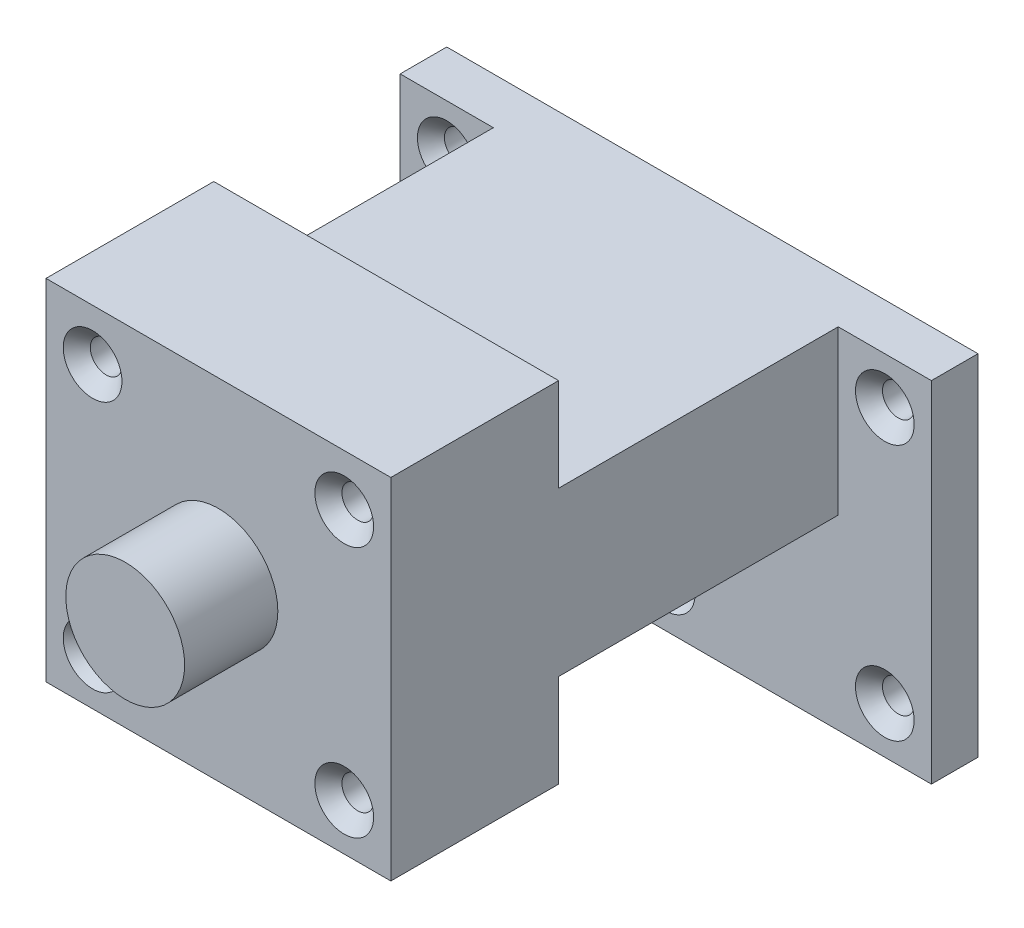
SolidWorks part; units mm, degrees
ref_plane "Plan de face" through (0, 0, 0) normal (0, 0, 1) x (1, 0, 0)
ref_plane "Plan de dessus" through (0, 0, 0) normal (0, 1, 0) x (1, 0, 0)
ref_plane "Plan de droite" through (0, 0, 0) normal (1, 0, 0) x (0, 0, -1)
sketch "Esquisse1" plane through (0, 0, 0) normal (0, 0, 1) x (1, 0, 0)
  line L2 (0, 0) -> (37, 0)
  line L3 (0, 0) -> (0, 37.5)
  line L4 (0, 37.5) -> (37, 37.5)
  line L5 (37, 0) -> (37, 37.5)
  dimension "D1" = 37.5
  dimension "D2" = 37
extrude "Boss.-Extru.1" add sketch "Esquisse1" along normal blind 53
sketch "Esquisse2" plane through (0, 0, 53) normal (0, 0, 1) x (1, 0, 0)
  line L0 (37, 0) -> (37, 37.5) construction
  line L4 (37, 37.5) -> (0, 37.5) construction
  circle A0 centre (18.5, 19) radius 6.375
  dimension "D3" = 12.75
  dimension "D1" = 18.5
  dimension "D2" = 18.5
extrude "Boss.-Extru.2" add sketch "Esquisse2" along normal blind 10
sketch "Esquisse3" plane through (0, 0, 53) normal (0, 0, 1) x (1, 0, 0)
  line L0 (37, 37.5) -> (0, 37.5) construction
  line L1 (0, 37.5) -> (0, 0) construction
  line L2 (37, 0) -> (37, 37.5) construction
  circle A0 centre (5, 32) radius 1.5
  circle A1 centre (32, 32) radius 1.5
  circle A2 centre (32, 5) radius 1.5
  circle A3 centre (5, 5) radius 1.5
  dimension "D3" = 3
  dimension "D5" = 3
  dimension "D9" = 3
  dimension "D11" = 3
  dimension "D1" = 5.5
  dimension "D2" = 5.5
  dimension "5" = 5
  dimension "D4" = 5
  dimension "D6" = 5
  dimension "D7" = 5
  dimension "D8" = 27
  dimension "D10" = 27
sketch "Esquisse6" plane through (0, 0, 0) normal (0, -1, 0) x (1, 0, 0)
  line L1 (0, 0) -> (10, 0)
  line L2 (0, 0) -> (0, 5)
  line L3 (0, 5) -> (10, 5)
  line L4 (10, 0) -> (10, 5)
  line L5 (37, 0) -> (27, 0)
  line L6 (37, 0) -> (37, 5)
  line L7 (37, 5) -> (27, 5)
  line L8 (27, 0) -> (27, 5)
  dimension "D1" = 10
  dimension "D2" = 5
  dimension "D3" = 10
  dimension "D4" = 5
extrude "Boss.-Extru.3" [suppressed] add sketch "Esquisse6" along normal blind 10
sketch "Esquisse7" plane through (0, 37.5, 0) normal (0, 1, 0) x (1, 0, 0)
  line L1 (0, 0) -> (10, 0)
  line L2 (0, 0) -> (0, -5)
  line L3 (0, -5) -> (10, -5)
  line L4 (10, 0) -> (10, -5)
  line L5 (37, 0) -> (27, 0)
  line L6 (37, 0) -> (37, -5)
  line L7 (37, -5) -> (27, -5)
  line L8 (27, 0) -> (27, -5)
  dimension "D1" = 5
  dimension "D2" = 5
  dimension "D3" = 10
  dimension "D4" = 10
extrude "Boss.-Extru.4" [suppressed] add sketch "Esquisse7" along normal blind 10
sketch "Esquisse8" [suppressed] plane through (0, 0, 5) normal (0, 0, 1) x (1, 0, 0)
  line L0 (37, -10) -> (27, -10) construction
  line L1 (37, -10) -> (37, 0) construction
  circle A0 centre (32, -5) radius 2.6226
  circle A1 centre (4.4036, -5.1811) radius 2.9344
  circle A2 centre (4.4036, 42.3532) radius 2.5459
  circle A3 centre (32.4325, 42.3532) radius 2.5419
  dimension "D1" = 5
  dimension "5" = 5
sketch "Esquisse10" plane through (0, 0, 0) normal (0, 0, -1) x (-1, 0, 0)
  line L0 (0, 37.5) -> (0, 0) construction
  line L1 (-37, 0) -> (-27, 0)
  line L2 (-37, 0) -> (-37, 10)
  line L3 (-37, 10) -> (-27, 10)
  line L4 (-27, 0) -> (-27, 10)
  line L5 (-37, 37.5) -> (0, 37.5)
  line L6 (-37, 37.5) -> (-37, 27.5)
  line L7 (-37, 27.5) -> (0, 27.5)
  line L8 (0, 37.5) -> (0, 27.5)
  line L13 (0, 0) -> (-10, 0)
  line L14 (0, 0) -> (0, 10)
  line L15 (0, 10) -> (-10, 10)
  line L16 (-10, 0) -> (-10, 10)
  dimension "D1" = 10
  dimension "D5" = 10
  dimension "D6" = 10
  dimension "10" = 10
  dimension "D7" = 10
extrude "Enlèv. mat.-Extru.1" cut sketch "Esquisse10" against normal blind 30 from offset 5 offset against normal yes
hole_wizard "Fraisage pour vis à tête fraisée bombée M31" positions "Esquisse4" profile "Esquisse5" countersink size "M3" standard "ISO"
sketch "Esquisse4" plane through (0, 0, 53) normal (0, 0, 1) x (1, 0, 0)
  point P0 (5, 32)
  point P3 (32, 32)
  point P6 (32, 5)
  point P9 (5, 5)
sketch "Esquisse5" plane through (5, 32, 53) normal (1, 0, 0) x (0, -1, 0)
  line L0 (0, 0) -> (0, 19.0215)
  line L1 (0, 19.0215) -> (1.7, 18)
  line L2 (1.7, 18) -> (1.7, 1.45)
  line L3 (1.7, 1.45) -> (3.15, 0)
  line L5 (3.15, 0) -> (0, 0)
  line L6 (-1.7, 1.45) -> (-3.15, 0) construction
  line L10 (0, 19.0215) -> (-1.7, 18) construction
  line L11 (0, -6.35) -> (0, 107.95) construction
  dimension "Diamètre du perçage" = 3.4
  dimension "Profondeur du perçage" = 18
  dimension "Diamètre du fraisage entrant" = 6.3
  dimension "Angle du fraisage entrant" = 90
  dimension "Angle de pointe" = 118
sketch "Esquisse11" plane through (0, 0, 0) normal (0, 0, -1) x (-1, 0, 0)
  line L8 (-37, 27.5) -> (0, 27.5) construction
  line L9 (-37, 27.5) -> (-47, 27.5)
  line L12 (-47, 27.5) -> (-47, -10)
  line L13 (0, 27.5) -> (10, 27.5)
  line L16 (10, 27.5) -> (10, -10)
  line L22 (-47, -10) -> (10, -10)
  line L23 (0, 0) -> (-37, 0) construction
  line L25 (-37, 0) -> (0, 0)
  line L26 (-37, 27.5) -> (-37, 0)
  line L28 (0, 27.5) -> (0, 0)
  dimension "D1" = 10
  dimension "D2" = 10
  dimension "D3" = 10
extrude "Boss.-Extru.5" add sketch "Esquisse11" against normal blind 5
sketch "Esquisse12" plane through (0, 0, 0) normal (0, 0, -1) x (-1, 0, 0)
  line L1 (-37, 37.5) -> (0, 37.5)
  line L2 (-37, 37.5) -> (-37, 27.5)
  line L3 (-37, 27.5) -> (0, 27.5)
  line L4 (0, 37.5) -> (0, 27.5)
extrude "Enlèv. mat.-Extru.2" cut sketch "Esquisse12" against normal up to surface (5 mm away) up to face at (18.5, 32.5, 5)
sketch "Esquisse13" plane through (0, 0, 5) normal (0, 0, 1) x (1, 0, 0)
  line L0 (-10, 27.5) -> (0, 27.5) construction
  line L1 (-10, -10) -> (-10, 27.5) construction
  line L2 (47, -10) -> (-10, -10) construction
  line L3 (47, 27.5) -> (47, -10) construction
  line L6 (37, 27.5) -> (47, 27.5) construction
  circle A0 centre (-5, 22.5) radius 1.5
  circle A1 centre (-5, -5) radius 1.5
  circle A2 centre (18.5, -5) radius 1.5
  circle A3 centre (42, -5) radius 1.5
  circle A4 centre (42, 22.5) radius 1.5
  dimension "D5" = 3
  dimension "D6" = 3
  dimension "D9" = 3
  dimension "D12" = 3
  dimension "D15" = 3
  dimension "D1" = 5
  dimension "D2" = 5
  dimension "D3" = 5
  dimension "D4" = 5
  dimension "D7" = 5
  dimension "D8" = 28.5
  dimension "D10" = 5
  dimension "D11" = 5
  dimension "D13" = 5
  dimension "D14" = 5
hole_wizard "Fraisage pour vis à tête fraisée bombée M32" positions "Esquisse14" profile "Esquisse15" countersink size "M3" standard "ISO"
sketch "Esquisse14" plane through (0, 0, 5) normal (0, 0, 1) x (1, 0, 0)
  point P0 (-5, 22.5)
  point P3 (-5, -5)
  point P6 (18.5, -5)
  point P9 (42, -5)
  point P12 (42, 22.5)
sketch "Esquisse15" plane through (-5, 22.5, 5) normal (1, 0, 0) x (0, -1, 0)
  line L0 (0, 0) -> (0, 6.0215)
  line L1 (0, 6.0215) -> (1.7, 5)
  line L2 (1.7, 5) -> (1.7, 1.45)
  line L3 (1.7, 1.45) -> (3.15, 0)
  line L5 (3.15, 0) -> (0, 0)
  line L6 (-1.7, 1.45) -> (-3.15, 0) construction
  line L10 (0, 6.0215) -> (-1.7, 5) construction
  line L11 (0, -6.35) -> (0, 107.95) construction
  dimension "Diamètre du perçage" = 3.4
  dimension "Profondeur du perçage" = 5
  dimension "Diamètre du fraisage entrant" = 6.3
  dimension "Angle du fraisage entrant" = 90
  dimension "Angle de pointe" = 118
